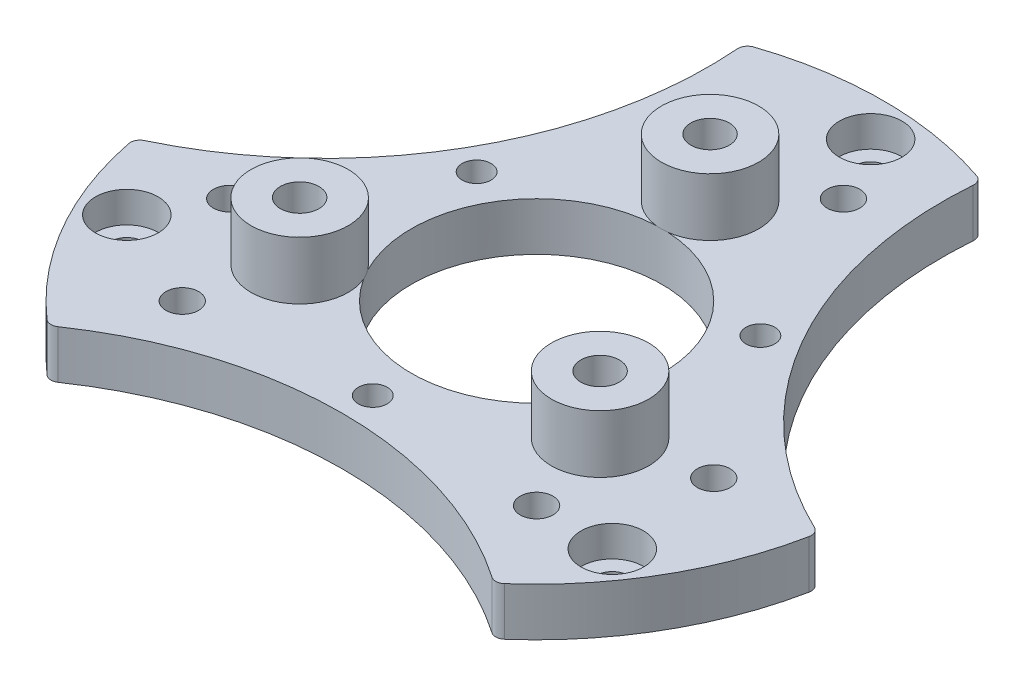
SolidWorks part; units mm, degrees
ref_plane "Front Plane" through (0, 0, 0) normal (0, 0, 1) x (1, 0, 0)
ref_plane "Top Plane" through (0, 0, 0) normal (0, 1, 0) x (1, 0, 0)
ref_plane "Right Plane" through (0, 0, 0) normal (1, 0, 0) x (0, 0, -1)
sketch "Sketch1" plane through (0, 0, 0) normal (0, 1, 0) x (1, 0, 0)
  circle A0 centre (0, 0) radius 36
  circle A1 centre (0, 0) radius 13
  dimension "D1" = 72
  dimension "D2" = 26
extrude "Boss-Extrude1" add sketch "Sketch1" along normal blind 5
sketch "Sketch2" plane through (0, 5, 0) normal (0, 1, 0) x (1, 0, 0)
  line L0 (0, -1000) -> (0, 49000) construction
  line L1 (2.789, 31.8782) -> (0, 0) construction
  circle A0 centre (2.789, 31.8782) radius 1.65
  dimension "D1" = 3.3
  dimension "D2" = 32
  dimension "D3" = 5
extrude "Cut-Extrude1" cut sketch "Sketch2" against normal through all
pattern_circular "CirPattern1" count 3 over 360 about axis through (0, 5, 0) along (0, -1, 0) of "Cut-Extrude1" reverse direction yes
sketch "Sketch10" plane through (0, 5, 0) normal (0, 1, 0) x (1, 0, 0)
  line L0 (0, 0) -> (17101.0072, 46984.631) construction
  line L1 (0, 0) -> (-17101.0072, 46984.631) construction
  line L2 (0, 0) -> (0, 50000) construction
  line L3 (-9.5766, 26.3114) -> (-12.3127, 33.8289)
  line L4 (9.5766, 26.3114) -> (12.3127, 33.8289)
  line L5 (17.9981, -21.4492) -> (23.1404, -27.5776)
  line L6 (27.5746, -4.8621) -> (35.4531, -6.2513)
  line L7 (-27.5746, -4.8621) -> (-35.4531, -6.2513)
  line L8 (-17.9981, -21.4492) -> (-23.1404, -27.5776)
  arc A0 (-12.3127, 33.8289) -> (12.3127, 33.8289) centre (0, 0) cw
  circle A1 centre (0, 0) radius 36 construction
  arc A2 (-9.5766, 26.3114) -> (9.5766, 26.3114) centre (0, 0) cw
  arc A3 (35.4531, -6.2513) -> (23.1404, -27.5776) centre (0, 0) cw
  arc A4 (27.5746, -4.8621) -> (17.9981, -21.4492) centre (0, 0) cw
  arc A5 (-23.1404, -27.5776) -> (-35.4531, -6.2513) centre (0, 0) cw
  arc A6 (-17.9981, -21.4492) -> (-27.5746, -4.8621) centre (0, 0) cw
  point P26 (0, 0)
  dimension "D1" = 20
  dimension "D2" = 20
  dimension "D3" = 8
  dimension "D4" = 3
sketch "Sketch3" plane through (0, 5, 0) normal (0, 1, 0) x (1, 0, 0)
  line L0 (0, 0) -> (51.9615, 30) construction
  line L1 (-1000, 0) -> (49000, 0) construction
  circle A0 centre (51.9615, 30) radius 39.8333
  dimension "D3" = 60
extrude "Cut-Extrude2" cut sketch "Sketch3" against normal blind 10
pattern_circular "CirPattern2" count 3 over 360 about axis through (0, 5, 0) along (0, -1, 0) of "Cut-Extrude2"
fillet "Fillet1" radius 1 6 edges at (23.1404, 2.5, 27.5776) (-23.1404, 2.5, 27.5776) (-35.4531, 2.5, 6.2513) (-12.3127, 2.5, -33.8289) (35.4531, 2.5, 6.2513) (12.3127, 2.5, -33.8289)
sketch "Sketch4" plane through (0, 5, 0) normal (0, 1, 0) x (1, 0, 0)
  circle A0 centre (0, 0) radius 6 construction
  circle A1 centre (0, 18) radius 12 construction
  circle A2 centre (0, 18) radius 5.05
  dimension "D1" = 12
  dimension "D2" = 24
  dimension "D3" = 10.1
extrude "Boss-Extrude2" add sketch "Sketch4" along normal blind 6
sketch "Sketch7" plane through (0, 5, 0) normal (0, 1, 0) x (1, 0, 0)
  circle A0 centre (2.789, 31.8782) radius 3.25
  dimension "D1" = 6.5
extrude "Cut-Extrude5" cut sketch "Sketch7" against normal blind 3.2
pattern_circular "CirPattern3" count 3 over 360 about axis through (0, 5, 0) along (0, -1, 0) of "Cut-Extrude5", "Boss-Extrude2" reverse direction yes
sketch "Sketch8" plane through (0, 5, 0) normal (0, 1, 0) x (1, 0, 0)
  line L0 (14.7224, 8.5) -> (0, 0) construction
  line L1 (-1000, 0) -> (49000, 0) construction
  circle A0 centre (14.7224, 8.5) radius 1.5
  dimension "D3" = 3
  dimension "D1" = 30
  dimension "D2" = 17
extrude "Cut-Extrude6" cut sketch "Sketch8" against normal blind 10
sketch "Sketch12" plane through (0, 11, 0) normal (0, 1, 0) x (1, 0, 0)
  circle A0 centre (0, 18) radius 2
  dimension "D1" = 4
extrude "Cut-Extrude8" cut sketch "Sketch12" against normal through all
pattern_circular "CirPattern4" count 3 over 360 about axis through (0, 5, 0) along (0, -1, 0) of "Cut-Extrude6", "Cut-Extrude8" reverse direction yes
sketch "Sketch9" plane through (0, 5, 0) normal (0, 1, 0) x (1, 0, 0)
  line L0 (-5.7304, 32.4987) -> (0, 0) construction
  line L1 (-25.7839, 33.0244) -> (49214.6038, 8715.4333) construction
  line L2 (-23.1208, 32.4785) -> (49217.2669, 8714.8874) construction
  line L3 (0, -1000) -> (0, 49000) construction
  circle A0 centre (-5.7304, 32.4987) radius 4 construction
  circle A1 centre (-5.7304, 32.4987) radius 1.65
  arc A2 (11.5708, 34.0898) -> (-11.5708, 34.0898) centre (0, 0) ccw construction
  dimension "D1" = 8
  dimension "D2" = 3.3
  dimension "D3" = 1
  dimension "D4" = 10
sketch "Sketch13" plane through (0, 5, 0) normal (0, 1, 0) x (1, 0, 0)
  line L0 (6.7293, 25.1141) -> (0, 0) construction
  line L1 (0, 0) -> (0, 18) construction
  line L2 (-6.7293, 25.1141) -> (0, 0) construction
  circle A0 centre (6.7293, 25.1141) radius 1.7
  circle A1 centre (-6.7293, 25.1141) radius 1.7
  point P8 (0, 0)
  dimension "D1" = 3.4
  dimension "D2" = 26
  dimension "D3" = 15
extrude "Cut-Extrude9" cut sketch "Sketch13" against normal through all
pattern_circular "CirPattern5" count 3 over 360 about axis through (0, 5, 0) along (0, -1, 0) of "Cut-Extrude9" reverse direction yes
